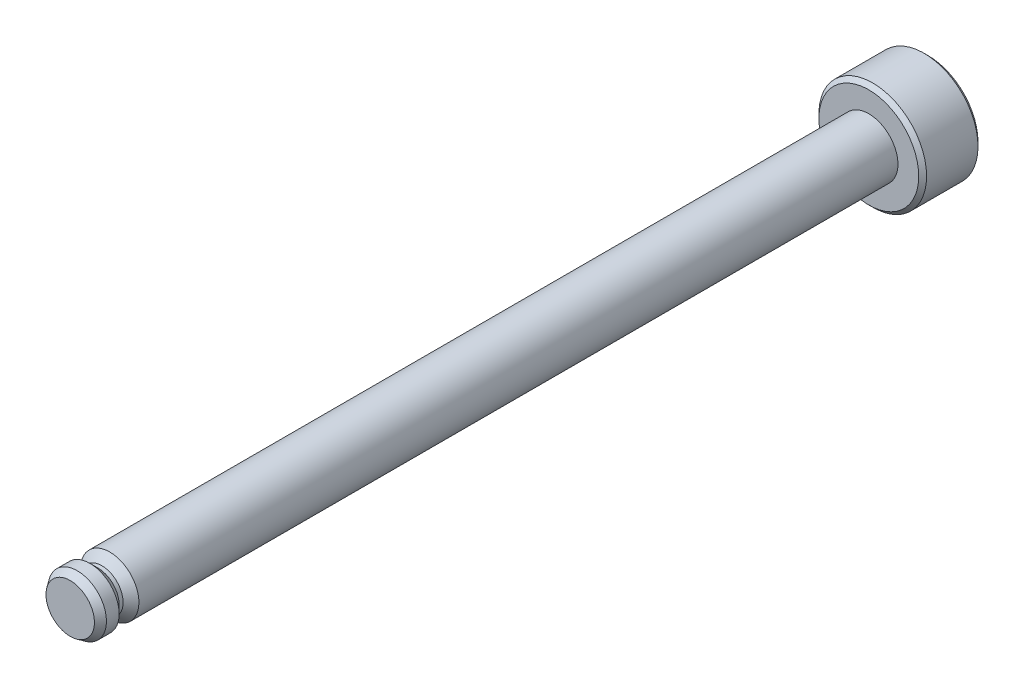
SolidWorks part; units mm, degrees
ref_plane "Front" through (0, 0, 0) normal (0, 0, 1) x (1, 0, 0)
ref_plane "Top" through (0, 0, 0) normal (0, 1, 0) x (1, 0, 0)
ref_plane "Right" through (0, 0, 0) normal (1, 0, 0) x (0, 0, -1)
sketch "Sketch2" plane through (0, 0, 0) normal (0, 0, 1) x (1, 0, 0)
  circle A0 centre (0, 0) radius 1.475
  dimension "D1" = 2.95
extrude "Shaft" add sketch "Sketch2" along normal blind 40.4
sketch "Sketch5" plane through (0, 0, 0) normal (0, 0, 1) x (1, 0, 0)
  circle A0 centre (0, 0) radius 2.725
  dimension "D1" = 5.45
extrude "Head" add sketch "Sketch5" against normal blind 3
chamfer "Chamfer1" distance 0.25 angle 55 1 edges at (1.475, 0, 40.4) first distance on face at (1.475, 0, 40.4)
chamfer "Deburs" distance 0.2 angle 45 2 edges at (2.725, 0, 0) (2.725, 0, -3)
sketch "Sketch6" plane through (0, 0, 0) normal (1, 0, 0) x (0, 0, -1)
  line L0 (0, 0) -> (-38.9, 0) construction
  line L1 (-38.9, 0) -> (-38.9, 1.075) construction
  line L2 (0, 1.475) -> (-40.043, 1.475) construction
  line L3 (-39.4, 1.475) -> (-38.4, 1.475)
  line L4 (-38.4, 1.475) -> (-38.8, 1.075)
  line L5 (-38.8, 1.075) -> (-39, 1.075)
  line L6 (-39, 1.075) -> (-39.4, 1.475)
  line L7 (-38.9, 1.075) -> (-38.9, 1.475) construction
  dimension "D1" = 38.9
  dimension "D2" = 0.4
  dimension "D3" = 1
revolve "e-Clip Notch Long" cut sketch "Sketch6" angle 360 about L0
equation "\"D1@Sketch2\"=\"Plastic Hardware OD@Box Assy.Assembly\""
equation "\"D1@Sketch5\"=\"Hardware Head Countersink Diameter@Box Assy.Assembly\"-.3mm"
equation "\"D1@Head\"=\"Countersink Depth@Box Assy.Assembly\""
equation "\"Length\" = 40mm"
equation "\"D1@Shaft\"=\"Length\"+.4mm"
equation "\"D1@Sketch6\"=\"Length\"-1.1mm"
